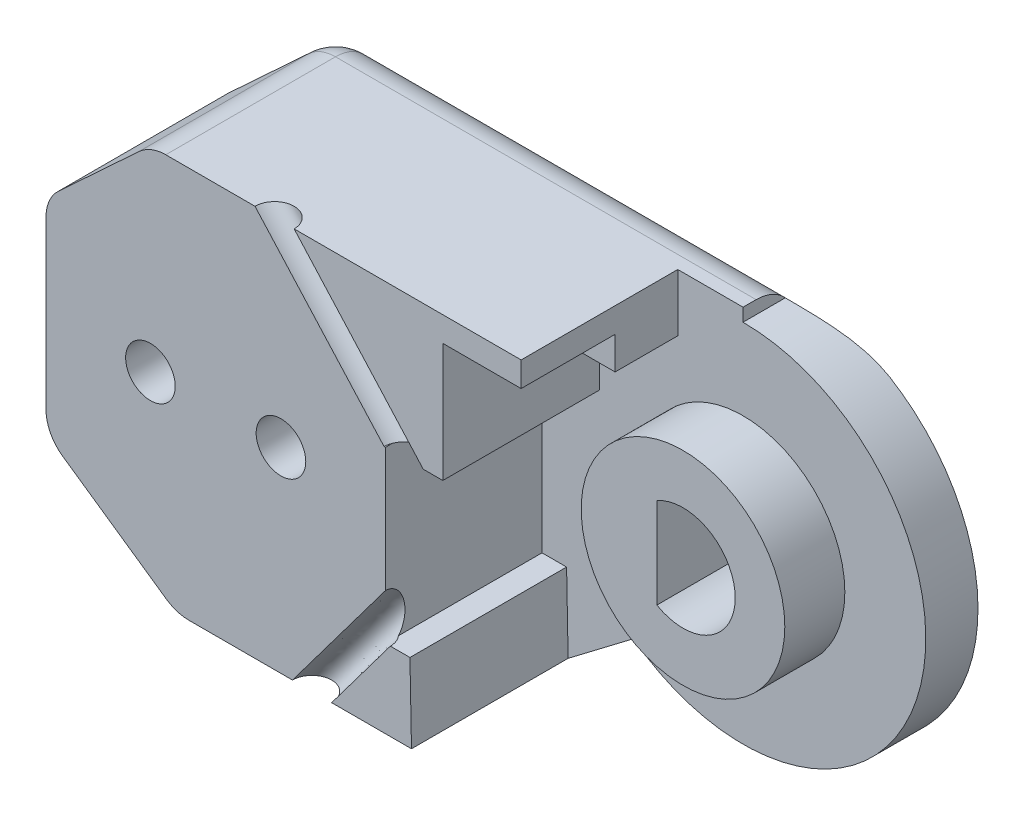
SolidWorks part; units mm, degrees
ref_plane "Front Plane" through (0, 0, 0) normal (0, 0, 1) x (1, 0, 0)
ref_plane "Top Plane" through (0, 0, 0) normal (0, 1, 0) x (1, 0, 0)
ref_plane "Right Plane" through (0, 0, 0) normal (1, 0, 0) x (0, 0, -1)
sketch "Sketch2" plane through (0, 0, 0) normal (0, 0, 1) x (1, 0, 0)
  line L1 (-2.5, 7.5) -> (-16.7, 7.5)
  line L2 (-20.7, 3.7934) -> (-20.7, -4.0316)
  line L3 (-15.7, -7.5) -> (-6.7, -7.5)
  line L4 (-6.7, -7.5) -> (-4.2, -5.6)
  line L5 (-2.5, 7.5) -> (0, 7.5)
  line L7 (0, 7) -> (0, 7.5)
  line L8 (-20.7, 3.7934) -> (-16.7, 7.5)
  line L9 (-20.7, -4.0316) -> (-15.7, -7.5)
  arc A1 (-4.2, -5.6) -> (7, 0) centre (0, 0) ccw
  arc A2 (7, 0) -> (0, 7) centre (0, 0) ccw
  dimension "D1" = 7
  dimension "D2" = 4
  dimension "D3" = 5
  dimension "D4" = 7.5
  dimension "D5" = 15
  dimension "D7" = 2.5
  dimension "D8" = 14
extrude "Boss-Extrude1" add sketch "Sketch2" along normal blind 2 contours A1 A2 L7 L5 L1 L8 L2 L9 L3 L4
sketch "Sketch4" plane through (0, 0, 2) normal (0, 0, 1) x (1, 0, 0)
  line L7 (-15.7, -7.5) -> (-6.7, -7.5)
  line L8 (-6.7, -7.5) -> (-6.7591, -4.5)
  line L9 (-6.7591, -4.5) -> (-7.7, -4.5)
  line L10 (-16.7, 7.5) -> (-2.5, 7.5)
  line L13 (-5.5, 2) -> (-5.5, 5.3)
  line L14 (-5.5, 5.3) -> (-2.5, 5.3)
  line L21 (-20.7, -4.0316) -> (-15.7, -7.5)
  line L24 (-16.7, 7.5) -> (-20.7, 3.7934)
  line L25 (-20.7, -4.0316) -> (-20.7, 3.7934)
  line L26 (-7.7, 2) -> (-5.5, 2)
  line L29 (-7.7, 2) -> (-7.7, -4.5)
  line L30 (-2.5, 7.5) -> (-2.5, 5.3)
  point P2 (-5.5, 3.65)
  dimension "D1" = 13
  dimension "D2" = 2.5
  dimension "D3" = 3
  dimension "D4" = 3
extrude "Boss-Extrude2" add sketch "Sketch4" along normal blind 6
ref_point "Point1"
sketch "Sketch22" plane through (0, 0, 2) normal (0, 0, 1) x (1, 0, 0)
  line L0 (0, 5.3) -> (-14, 5.3) construction
  line L1 (0, 4) -> (-14, 4) construction
  line L2 (-14, 4) -> (-14, 5.3) construction
  circle A0 centre (0, 0) radius 5.3 construction
  circle A1 centre (0, 0) radius 4 construction
  dimension "D1" = 14
  dimension "D2" = 10.6
  dimension "D3" = 8
sketch "Sketch24" plane through (0, 0, 2) normal (0, 0, 1) x (1, 0, 0)
  circle A0 centre (0, 0) radius 3.9
  dimension "D1" = 7.8
extrude "Boss-Extrude5" add sketch "Sketch24" along normal blind 2.3
sketch "Sketch29" plane through (-5.5, 0, 0) normal (1, 0, 0) x (0, 0, -1)
  line L0 (-1.9279, 3.9758) -> (-8, 3.9758) construction
  line L1 (-8, 2) -> (-8, 5.3) construction
sketch "Sketch30" plane through (-5.5, 0, 0) normal (1, 0, 0) x (0, 0, -1)
  line L0 (-4.4659, 3.9758) -> (-4.4659, 5.3)
  line L1 (-4.4659, 3.9758) -> (-2.0573, 3.9758)
  line L2 (-4.4659, 5.3) -> (-2.0573, 5.3)
  line L3 (-2.0573, 3.9758) -> (-2.0573, 5.3)
  line L4 (-1.9279, 3.9758) -> (-8, 3.9758) construction
  line L5 (-8, 5.3) -> (-2, 5.3) construction
extrude "Cut-Extrude12" cut sketch "Sketch30" against normal blind 8
ref_plane "Plane1" through (0, 0, 8) normal (0, 0, 1) x (1, 0, 0)
sketch "Sketch8" plane through (0, 0, 2) normal (0, 0, 1) x (1, 0, 0)
  circle A1 centre (0, 0) radius 3.8
  circle A2 centre (0, 0) radius 2.5
sketch "Sketch28" plane through (0, 0, 4.3) normal (0, 0, 1) x (1, 0, 0)
  line L0 (-1, 1.7321) -> (-1, -1.7321)
  arc A0 (-1, -1.7321) -> (-1, 1.7321) centre (0, 0) ccw
  dimension "D1" = 1
  dimension "D2" = 2
extrude "Cut-Extrude11" cut sketch "Sketch28" against normal through all
sketch "Sketch33" plane through (0, 0, 8) normal (0, 0, 1) x (1, 0, 0)
  line L0 (-7, 2) -> (-0.5657, -5.1566) construction
  line L2 (-8.2591, -4.5) -> (-2.6001, 3.0469) construction
  dimension "D1" = 1.5
  dimension "D2" = 1.5
fillet "Fillet1" radius 1.5 9 edges at (-11.2, -7.5, 0) (-8.35, 7.5, 0) (-18.7, 5.6467, 0) (-18.2, -5.7658, 0) (-20.7, -0.1191, 0) (-15.7, -7.5, 4) (-20.7, -4.0316, 4) (-20.7, 3.7934, 4) (-16.7, 7.5, 4)
sketch "Sketch34" plane through (0, 2, 0) normal (0, -1, 0) x (1, 0, 0)
  line L0 (-5.5, 1.9279) -> (-5.5, 8) construction
  circle A0 centre (-7, 8) radius 0.75
  dimension "D1" = 1.5
  dimension "D2" = 1.5
extrude "Cut-Extrude13" cut sketch "Sketch34" along direction (0.6686, -0.7436, 0) on the side against the normal blind 8
sketch "Sketch35" plane through (0, -4.5, 0) normal (0, 1, 0) x (1, 0, 0)
  circle A0 centre (-8.2591, -8) radius 0.75
extrude "Cut-Extrude14" cut sketch "Sketch35" along direction (0.5999, 0.8001, 0) on the side against the normal blind 8 and the other way blind 3
sketch "Sketch36" plane through (0, 0, 8) normal (0, 0, 1) x (1, 0, 0)
  line L2 (-7.7, -2.7542) -> (-7.7, 2) construction
  circle A0 centre (-11.7, 0) radius 0.95
  circle A1 centre (-16.7, 0) radius 0.95
  dimension "D1" = 4
  dimension "D2" = 5
extrude "Cut-Extrude15" cut sketch "Sketch36" against normal blind 8
sketch "Sketch37" plane through (0, 0, 0) normal (0, 0, -1) x (-1, 0, 0)
  circle A0 centre (11.7, 0) radius 2
  circle A1 centre (16.7, 0) radius 2
extrude "Cut-Extrude16" cut sketch "Sketch37" against normal blind 2.5
sketch "Sketch38" plane through (0, 0, 8) normal (0, 0, 1) x (1, 0, 0)
  line L0 (-5.5, 5.3) -> (-2.5, 5.3)
  line L1 (-5.5, 5.3) -> (-5.5, 6.55)
  line L2 (-2.5, 5.3) -> (-2.5, 6.55)
  line L3 (-5.5, 6.55) -> (-2.5, 6.55)
  dimension "D1" = 1.25
extrude "Cut-Extrude17" cut sketch "Sketch38" against normal blind 3.6
ref_plane "Plane2" through (0, 0, 4.4) normal (0, 0, 1) x (1, 0, 0)
